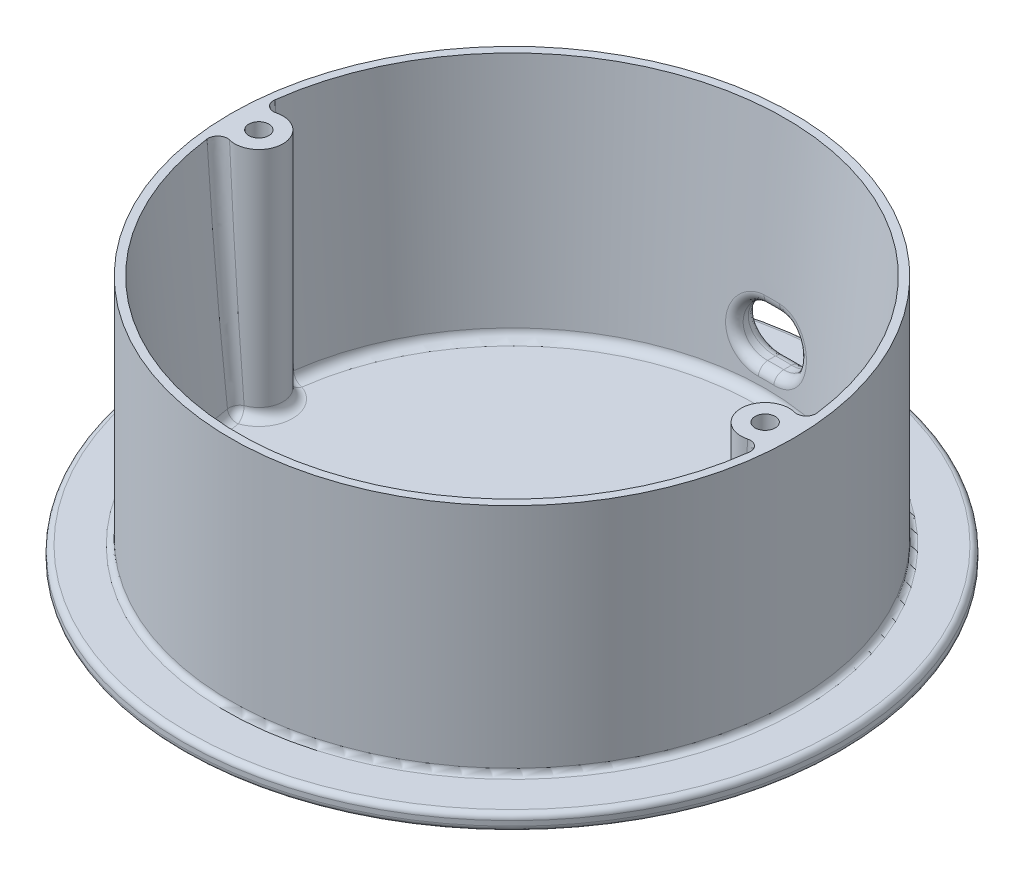
SolidWorks part; units mm, degrees
material "ABS"
ref_plane "Plan de face" through (0, 0, 0) normal (0, 0, 1) x (1, 0, 0)
ref_plane "Plan de dessus" through (0, 0, 0) normal (0, 1, 0) x (1, 0, 0)
ref_plane "Plan de droite" through (0, 0, 0) normal (1, 0, 0) x (0, 0, -1)
sketch "Esquisse10" plane through (0, 0, 0) normal (0, 0, 1) x (1, 0, 0)
  line L0 (0, 25) -> (0, -6) construction
  line L1 (41, -4) -> (41, -6)
  line L2 (34, 25) -> (35, 25)
  line L3 (4.15, -4) -> (4.15, -6)
  line L4 (4.15, -6) -> (41, -6)
  line L8 (41, -4) -> (35, -4)
  line L9 (35, 25) -> (35, -4)
  line L13 (4.15, -4) -> (31.4628, -4)
  line L14 (34, 25) -> (31.4628, -4)
  dimension "D1" = 2
  dimension "D2" = 6
  dimension "D3" = 8.3
  dimension "D4" = 70
  dimension "D5" = 25
  dimension "D6" = 5
  dimension "D7" = 31
  dimension "D8" = 6
  dimension "D9" = 1
  dimension "D10" = 2
  dimension "D11" = 82
revolve "Révolution1" add sketch "Esquisse10" angle 360 about L0
sketch "Esquisse11" plane through (0, 0, 0) normal (0, 0, 1) x (1, 0, 0)
  line L3 (1, 2) -> (-1, 2) construction
  line L4 (1, -1) -> (-1, -1)
  line L5 (1, 5) -> (-1, 5)
  line L6 (41, -4) -> (-41, -4) construction
  arc A2 (1, -1) -> (1, 5) centre (1, 2) ccw
  arc A3 (-1, 5) -> (-1, -1) centre (-1, 2) ccw
  point P7 (0, 2)
  dimension "D1" = 6
  dimension "D2" = 6
  dimension "D3" = 2
extrude "Enlèv. mat.-Extru.2" cut sketch "Esquisse11" against normal through all
sketch "Esquisse12" plane through (0, -4, 0) normal (0, 1, 0) x (1, 0, 0)
  line L0 (-7, 0) -> (7, 0) construction
  line L1 (-7, 1.75) -> (7, 1.75)
  line L2 (-7, -1.75) -> (7, -1.75)
  arc A0 (-7, 1.75) -> (-7, -1.75) centre (-7, 0) ccw
  arc A1 (7, -1.75) -> (7, 1.75) centre (7, 0) ccw
  point P2 (0, 0)
  dimension "D1" = 3.5
  dimension "D2" = 14
extrude "Enlèv. mat.-Extru.3" cut sketch "Esquisse12" against normal through all
sketch "Esquisse13" plane through (0, -4, 0) normal (0, 1, 0) x (1, 0, 0)
  line L0 (0, -17.05) -> (0, 17.05) construction
  circle A0 centre (-31.5, 0) radius 3
  circle A1 centre (31.5, 0) radius 3
  dimension "D1" = 63
  dimension "D2" = 6
extrude "Boss.-Extru.1" add sketch "Esquisse13" along normal up to surface (29 mm away) up to face at (-34, 25, 0)
fillet "Congé4" radius 1.2 16 edges at (-28.5, -4, 0) (0, -4, 31.4628) (28.5, -4, 0) (0, -4, -31.4628) (31.8466, 1.9768, 2.9799) (33.3991, 19.053, -2.3224) (-31.8466, 1.9768, -2.9799) (-33.3991, 19.053, 2.3224) (-3.9799, 1.6534, -34.773) (0, 5, -35) (3.9799, 2.3466, -34.773) (0, -1, -35) (0, -1, -31.7253) (3.9804, 1.6579, -31.709) (0, 5, -32.2502) (-3.9815, 2.3326, -31.7683)
fillet "Congé5" radius 0.7 3 edges at (-41, -6, 0) (-41, -4, 0) (-35, -4, 0)
sketch "Esquisse14" plane through (0, 25, 0) normal (0, 1, 0) x (1, 0, 0)
  line L0 (0, -17.05) -> (0, 17.05) construction
  circle A0 centre (-31.5, 0) radius 1.25
  circle A1 centre (31.5, 0) radius 1.25
  arc A2 (-32.2443, -2.9062) -> (-32.2443, 2.9062) centre (-31.5, 0) ccw construction
  dimension "D1" = 63
  dimension "D2" = 2.5
extrude "Enlèv. mat.-Extru.4" cut sketch "Esquisse14" against normal blind 25
sketch "Esquisse15" plane through (0, -6, 0) normal (0, -1, 0) x (1, 0, 0)
  circle A0 centre (0, 0) radius 10
  dimension "D1" = 20
extrude "Boss.-Extru.2" [suppressed] add sketch "Esquisse15" against normal blind 0.2
